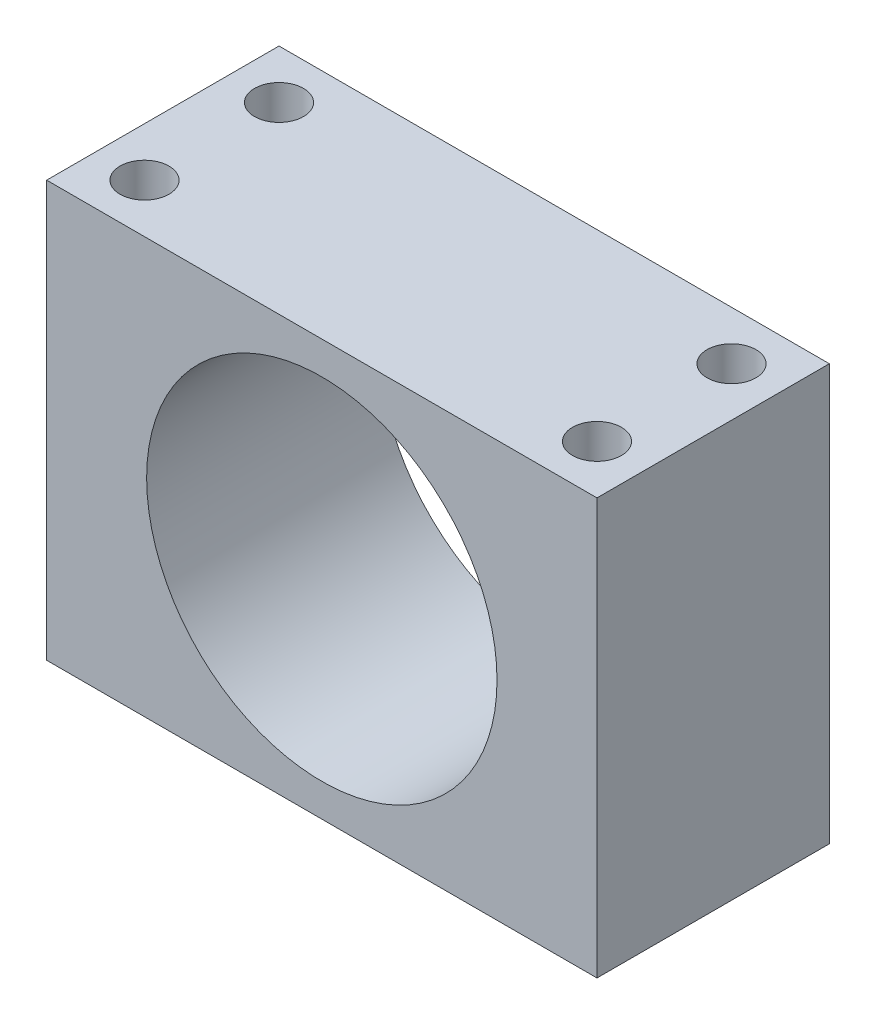
SolidWorks part; units mm, degrees
ref_plane "Front Plane" through (0, 0, 0) normal (0, 0, 1) x (1, 0, 0)
ref_plane "Top Plane" through (0, 0, 0) normal (0, 1, 0) x (1, 0, 0)
ref_plane "Right Plane" through (0, 0, 0) normal (1, 0, 0) x (0, 0, -1)
sketch "Sketch1" plane through (0, 0, 0) normal (0, 0, 1) x (1, 0, 0)
  line L1 (-45, -34) -> (45, -34)
  line L2 (-45, -34) -> (-45, 34)
  line L3 (-45, 34) -> (45, 34)
  line L4 (45, -34) -> (45, 34)
  line L5 (-45, -34) -> (45, 34) construction
  line L6 (-45, 34) -> (45, -34) construction
  circle A0 centre (0, 0) radius 28.65
  point P0 (0, 0)
  dimension "D3" = 57.3
  dimension "D1" = 90
  dimension "D2" = 68
extrude "Boss-Extrude1" add sketch "Sketch1" along normal mid plane 38
sketch "Sketch2" plane through (0, 34, 0) normal (0, 1, 0) x (1, 0, 0)
  line L0 (-37, 19) -> (-37, -19) construction
  line L1 (45, 19) -> (-45, 19) construction
  line L2 (45, -19) -> (-45, -19) construction
  line L3 (37, 19) -> (37, -19) construction
  line L4 (-45, -19) -> (-45, 19) construction
  line L5 (45, -19) -> (45, 19) construction
  line L6 (-45, 11) -> (45, 11) construction
  line L7 (-45, -11) -> (45, -11) construction
  circle A0 centre (-37, 11) radius 4
  circle A1 centre (-37, -11) radius 4
  circle A2 centre (37, 11) radius 4
  circle A3 centre (37, -11) radius 4
  dimension "D5" = 8
  dimension "D6" = 8
  dimension "D7" = 8
  dimension "D8" = 8
  dimension "D1" = 8
  dimension "D2" = 8
  dimension "D3" = 8
  dimension "D4" = 8
extrude "Cut-Extrude1" cut sketch "Sketch2" against normal through all
equation "\"D6@Sketch2\"=\"D5@Sketch2\""
equation "\"D7@Sketch2\"=\"D5@Sketch2\""
equation "\"D8@Sketch2\"=\"D5@Sketch2\""
